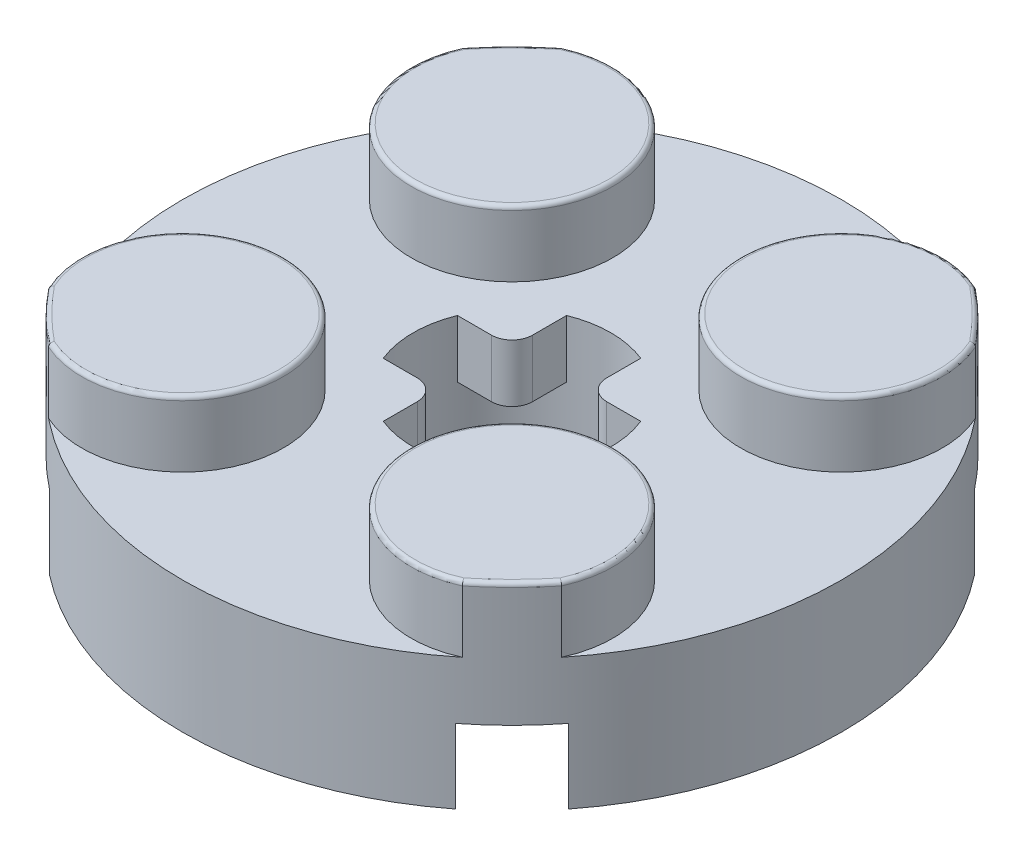
SolidWorks part; units mm, degrees
material "PET"
ref_plane "Alzado" through (0, 0, 0) normal (0, 0, 1) x (1, 0, 0)
ref_plane "Planta" through (0, 0, 0) normal (0, 1, 0) x (1, 0, 0)
ref_plane "Vista lateral" through (0, 0, 0) normal (1, 0, 0) x (0, 0, -1)
sketch "Croquis1" plane through (0, 0, 0) normal (0, 1, 0) x (1, 0, 0)
  line L1 (-4, 4) -> (4, 4)
  line L2 (-4, 4) -> (-4, -4)
  line L3 (-4, -4) -> (4, -4)
  line L4 (4, 4) -> (4, -4)
  line L5 (-4, 4) -> (4, -4) construction
  line L6 (-4, -4) -> (4, 4) construction
  point P0 (0, 0)
  dimension "D1" = 8
extrude "Saliente-Extruir1" add sketch "Croquis1" along normal blind 3.2
sketch "Croquis2" plane through (0, 3.2, 0) normal (0, 1, 0) x (1, 0, 0)
  circle A0 centre (0, 0) radius 2.45
  dimension "D1" = 4.9
extrude "Saliente-Extruir2" add sketch "Croquis2" along normal blind 1.6
mirror "Simetría1" about plane through (4, 3.2, -4) normal (-1, 0, 0) of "Saliente-Extruir2", "Saliente-Extruir1"
mirror "Simetría2" about plane through (-4, 3.2, -4) normal (0, 0, 1) of bodies 105
sketch "Croquis3" plane through (0, 0, 0) normal (0, -1, 0) x (1, 0, 0)
  line L1 (-2.3, -10.3) -> (10.3, -10.3)
  line L2 (-2.3, -10.3) -> (-2.3, 2.3)
  line L3 (-2.3, 2.3) -> (10.3, 2.3)
  line L4 (10.3, -10.3) -> (10.3, 2.3)
  line L5 (-2.3, -10.3) -> (10.3, 2.3) construction
  line L6 (-2.3, 2.3) -> (10.3, -10.3) construction
  line L7 (-4, -12) -> (12, -12) construction
  line L12 (-4, -12) -> (-4, 4) construction
  line L13 (-4, 4) -> (12, 4) construction
  point P0 (4, -4)
  dimension "D1" = 8
  dimension "D2" = 1.7
  dimension "D3" = 8
extrude "Cortar-Extruir1" cut sketch "Croquis3" against normal blind 1.8
sketch "Croquis4" plane through (0, 1.8, 0) normal (0, -1, 0) x (1, 0, 0)
  line L0 (-4, 4) -> (12, 4) construction
  line L1 (-4, -12) -> (-4, 4) construction
  line L2 (4, 2.3) -> (4, -10.3) construction
  line L3 (10.3, 2.3) -> (-2.3, 2.3) construction
  line L4 (-2.3, -10.3) -> (10.3, -10.3) construction
  line L5 (-2.3, -4) -> (10.3, -4) construction
  line L6 (-2.3, 2.3) -> (-2.3, -10.3) construction
  line L7 (10.3, -10.3) -> (10.3, 2.3) construction
  circle A0 centre (0, 0) radius 1.6
  circle A1 centre (8, 0) radius 1.6
  circle A2 centre (0, -8) radius 1.6
  circle A3 centre (8, -8) radius 1.6
  dimension "D1" = 3.2
  dimension "D2" = 4
  dimension "D4" = 2
  dimension "D3" = 4
  dimension "D5" = 2
sketch "Croquis5" plane through (0, 0, 0) normal (0, -1, 0) x (1, 0, 0)
  line L0 (-4, -12) -> (-4, 4) construction
  line L1 (-4, 4) -> (12, 4) construction
  circle A0 centre (4, -4) radius 3.267
  circle A1 centre (4, -4) radius 2.4
  dimension "D1" = 4.8
  dimension "D2" = 8
  dimension "D3" = 8
  dimension "D4" = 6.534
extrude "Saliente-Extruir3" add sketch "Croquis5" against normal up to next
sketch "Croquis6" plane through (0, 3.2, 0) normal (0, 1, 0) x (1, 0, 0)
  line L0 (-4, 12) -> (12, 12) construction
  line L1 (-4, 12) -> (-4, -4) construction
  line L2 (-4, -4) -> (12, -4) construction
  circle A0 centre (4, 4) radius 8
extrude "Cortar-Extruir3" cut sketch "Croquis6" against normal blind 10 flip side to cut
sketch "Croquis7" plane through (0, 3.2, 0) normal (0, 1, 0) x (1, 0, 0)
  line L0 (4, -4) -> (4, 4) construction
  arc A0 (-1.0239, -2.2258) -> (9.0239, -2.2258) centre (4, 4) ccw construction
  line B0 (1.7751, 4.9) -> (1.7751, 3.1) construction
  line B1 (4.9, 6.2249) -> (3.1, 6.2249) construction
  line B2 (6.2249, 4.9) -> (6.2249, 3.1) construction
  line B3 (4.9, 1.7751) -> (3.1, 1.7751) construction
  line B4 (2.6, 4.9) -> (1.7751, 4.9)
  line B5 (4.9, 1.7751) -> (4.9, 2.6)
  line B6 (3.1, 1.7751) -> (3.1, 2.6)
  line B7 (4.9, 1.7751) -> (3.1, 6.2249) construction
  line B8 (4.9, 6.2249) -> (3.1, 1.7751) construction
  line B9 (6.2249, 4.9) -> (5.4, 4.9)
  line B10 (6.2249, 3.1) -> (5.4, 3.1)
  line B11 (6.2249, 4.9) -> (1.7751, 3.1) construction
  line B12 (6.2249, 3.1) -> (1.7751, 4.9) construction
  line B13 (3.1, 5.4) -> (3.1, 6.2249)
  line B14 (4.9, 5.4) -> (4.9, 6.2249)
  line B15 (2.6, 3.1) -> (1.7751, 3.1)
  arc B16 (1.7751, 4.9) -> (1.7751, 3.1) centre (4, 4) ccw
  arc B17 (2.6, 3.1) -> (3.1, 2.6) centre (2.6, 2.6) cw
  arc B18 (4.9, 2.6) -> (5.4, 3.1) centre (5.4, 2.6) cw
  arc B19 (5.4, 4.9) -> (4.9, 5.4) centre (5.4, 5.4) cw
  arc B20 (3.1, 5.4) -> (2.6, 4.9) centre (2.6, 5.4) cw
  arc B21 (4.9, 6.2249) -> (3.1, 6.2249) centre (4, 4) ccw
  arc B22 (6.2249, 3.1) -> (6.2249, 4.9) centre (4, 4) ccw
  arc B23 (3.1, 1.7751) -> (4.9, 1.7751) centre (4, 4) ccw
sketch_block_instance "kereszt-metszet-1"
sketch_block "Bloque1" parameters "D1"=4.8, "D3"=0.5, "D2"=1.8
extrude "Cortar-Extruir4" cut sketch "Croquis7" against normal through all
sketch "Croquis10" plane through (0, 4.8, 0) normal (0, 1, 0) x (1, 0, 0)
  arc A2 (10.1035, -0.6446) -> (8.6446, -2.1035) centre (8, 0) ccw construction
  arc A3 (8.6446, 10.1035) -> (10.1035, 8.6446) centre (8, 8) ccw construction
  line B0 (-1.3419, 8.88) -> (-1.7347, 7.12) construction
  line B1 (-1.2247, 8.8539) -> (-1.585, 7.24)
  line B2 (-1.459, 8.9061) -> (-1.8518, 7.1461)
  line B3 (-1.7347, 7.12) -> (-1.2347, 7.12) construction
  line B4 (-0.4503, 8.88) -> (-0.8432, 7.12) construction
  line B5 (-1.7347, 7) -> (-1.2347, 7)
  line B6 (-0.3542, 8.76) -> (-0.497, 8.12)
  line B7 (-1.585, 7.24) -> (-1.2347, 7.24)
  line B8 (-0.5675, 8.9061) -> (-0.9603, 7.1461)
  line B9 (-0.4503, 8.88) -> (0.0497, 8.88) construction
  line B10 (-0.4503, 9) -> (0.0497, 9)
  line B11 (-0.3542, 8.76) -> (0.0497, 8.76)
  line B12 (-0.6468, 8) -> (-0.3468, 8) construction
  line B13 (-0.5506, 7.88) -> (-0.6935, 7.24)
  line B14 (-0.5506, 7.88) -> (-0.3468, 7.88)
  line B15 (-0.8432, 7.12) -> (-0.3432, 7.12) construction
  line B16 (1.3043, 8.6845) -> (1.0231, 7.4245) construction
  line B17 (-0.8432, 7) -> (-0.3432, 7)
  line B18 (-0.497, 8.12) -> (-0.3468, 8.12)
  line B19 (-0.6935, 7.24) -> (-0.3432, 7.24)
  line B20 (1.4214, 8.6583) -> (1.1402, 7.3983)
  line B21 (1.1872, 8.7106) -> (0.9059, 7.4506)
  line B22 (0.3974, 8.684) -> (0.1163, 7.4245) construction
  line B23 (0.5145, 8.6578) -> (0.2334, 7.3983)
  line B24 (0.2803, 8.7101) -> (-0.0008, 7.4506)
  line B25 (0.6043, 7.3155) -> (0.7571, 8) construction
  line B26 (0.4872, 7.3417) -> (0.6073, 7.88)
  line B27 (0.7214, 7.2894) -> (0.8742, 7.9739)
  line B28 (1.7923, 8.5755) -> (1.5111, 7.3155) construction
  line B29 (1.9094, 8.5494) -> (1.6282, 7.2894)
  line B30 (1.6752, 8.6017) -> (1.3939, 7.3417)
  line B31 (-1.347, 9) -> (1.5483, 9) construction
  line B32 (-1.7347, 7) -> (1.2671, 7) construction
  line B33 (0.7571, 8) -> (0.5771, 8) construction
  line B34 (0.7571, 8.12) -> (0.5771, 8.12)
  line B35 (0.6073, 7.88) -> (0.5771, 7.88)
  line B36 (-1.1147, 7.12) -> (-0.6951, 9) construction
  line B37 (-0.2232, 7.12) -> (0.1583, 8.829) construction
  arc B38 (-1.459, 8.9061) -> (-1.2247, 8.8539) centre (-1.3419, 8.88) cw
  arc B39 (-1.8518, 7.1461) -> (-1.7347, 7) centre (-1.7347, 7.12) ccw
  arc B40 (-1.2347, 7) -> (-1.2347, 7.24) centre (-1.2347, 7.12) ccw
  arc B41 (0.8742, 7.9739) -> (0.7571, 8.12) centre (0.7571, 8) ccw
  arc B42 (0.0497, 8.76) -> (0.0497, 9) centre (0.0497, 8.88) ccw
  arc B43 (0.5771, 8.12) -> (0.5771, 7.88) centre (0.5771, 8) ccw
  arc B44 (-0.3468, 7.88) -> (-0.3468, 8.12) centre (-0.3468, 8) ccw
  arc B45 (-0.9603, 7.1461) -> (-0.8432, 7) centre (-0.8432, 7.12) ccw
  arc B46 (-0.3432, 7) -> (-0.3432, 7.24) centre (-0.3432, 7.12) ccw
  arc B47 (-0.4503, 9) -> (-0.5675, 8.9061) centre (-0.4503, 8.88) ccw
  arc B48 (0.3974, 8.684) -> (0.891, 8.6) centre (0.6421, 8.6293) cw construction
  arc B49 (1.0102, 8.586) -> (0.2803, 8.7101) centre (0.6421, 8.6293) ccw
  arc B50 (0.7718, 8.614) -> (0.5145, 8.6578) centre (0.6421, 8.6293) ccw
  arc B51 (0.7718, 8.614) -> (1.0102, 8.586) centre (0.891, 8.6) ccw
  arc B52 (0.1163, 7.4245) -> (0.6043, 7.3155) centre (0.3603, 7.37) ccw construction
  arc B53 (-0.0008, 7.4506) -> (0.7214, 7.2894) centre (0.3603, 7.37) ccw
  arc B54 (0.2334, 7.3983) -> (0.4872, 7.3417) centre (0.3603, 7.37) ccw
  arc B55 (1.0231, 7.4245) -> (1.5111, 7.3155) centre (1.2671, 7.37) ccw construction
  arc B56 (0.9059, 7.4506) -> (1.6282, 7.2894) centre (1.2671, 7.37) ccw
  arc B57 (1.1402, 7.3983) -> (1.3939, 7.3417) centre (1.2671, 7.37) ccw
  arc B58 (1.3043, 8.6845) -> (1.7923, 8.5755) centre (1.5483, 8.63) cw construction
  arc B59 (1.9094, 8.5494) -> (1.1872, 8.7106) centre (1.5483, 8.63) ccw
  arc B60 (1.6752, 8.6017) -> (1.4214, 8.6583) centre (1.5483, 8.63) ccw
  circle B61 centre (-0.0325, 7.9745) radius 2.4 construction
  line B62 (-1.1923, 0.8794) -> (-1.5525, -0.7345)
  line B63 (-1.4265, 0.9317) -> (-1.8194, -0.8283)
  line B64 (-1.7023, -0.9745) -> (-1.2023, -0.9745)
  line B65 (-0.3217, 0.7855) -> (-0.4646, 0.1455)
  line B66 (-1.5525, -0.7345) -> (-1.2023, -0.7345)
  line B67 (-0.535, 0.9317) -> (-0.9279, -0.8283)
  line B68 (-0.4179, 1.0255) -> (0.0821, 1.0255)
  line B69 (-0.3217, 0.7855) -> (0.0821, 0.7855)
  line B70 (-0.5181, -0.0945) -> (-0.661, -0.7345)
  line B71 (-0.5181, -0.0945) -> (-0.3143, -0.0945)
  line B72 (-0.8107, -0.9745) -> (-0.3107, -0.9745)
  line B73 (-0.4646, 0.1455) -> (-0.3143, 0.1455)
  line B74 (-0.661, -0.7345) -> (-0.3107, -0.7345)
  line B75 (1.4539, 0.6838) -> (1.1726, -0.5762)
  line B76 (1.2197, 0.7361) -> (0.9384, -0.5239)
  line B77 (0.547, 0.6833) -> (0.2659, -0.5762)
  line B78 (0.3128, 0.7356) -> (0.0316, -0.5239)
  line B79 (0.5196, -0.6328) -> (0.6398, -0.0945)
  line B80 (0.7539, -0.6851) -> (0.9066, -0.0006)
  line B81 (1.9419, 0.5749) -> (1.6606, -0.6851)
  line B82 (1.7077, 0.6272) -> (1.4264, -0.6328)
  line B83 (0.7895, 0.1455) -> (0.6095, 0.1455)
  line B84 (0.6398, -0.0945) -> (0.6095, -0.0945)
  arc B85 (-1.4265, 0.9317) -> (-1.1923, 0.8794) centre (-1.3094, 0.9055) cw
  arc B86 (-1.8194, -0.8283) -> (-1.7023, -0.9745) centre (-1.7023, -0.8545) ccw
  arc B87 (-1.2023, -0.9745) -> (-1.2023, -0.7345) centre (-1.2023, -0.8545) ccw
  arc B88 (0.9066, -0.0006) -> (0.7895, 0.1455) centre (0.7895, 0.0255) ccw
  arc B89 (0.0821, 0.7855) -> (0.0821, 1.0255) centre (0.0821, 0.9055) ccw
  arc B90 (0.6095, 0.1455) -> (0.6095, -0.0945) centre (0.6095, 0.0255) ccw
  arc B91 (-0.3143, -0.0945) -> (-0.3143, 0.1455) centre (-0.3143, 0.0255) ccw
  arc B92 (-0.9279, -0.8283) -> (-0.8107, -0.9745) centre (-0.8107, -0.8545) ccw
  arc B93 (-0.3107, -0.9745) -> (-0.3107, -0.7345) centre (-0.3107, -0.8545) ccw
  arc B94 (-0.4179, 1.0255) -> (-0.535, 0.9317) centre (-0.4179, 0.9055) ccw
  arc B95 (1.0426, 0.6115) -> (0.3128, 0.7356) centre (0.6745, 0.6549) ccw
  arc B96 (0.8043, 0.6396) -> (0.547, 0.6833) centre (0.6745, 0.6549) ccw
  arc B97 (0.8043, 0.6396) -> (1.0426, 0.6115) centre (0.9235, 0.6255) ccw
  arc B98 (0.0316, -0.5239) -> (0.7539, -0.6851) centre (0.3927, -0.6045) ccw
  arc B99 (0.2659, -0.5762) -> (0.5196, -0.6328) centre (0.3927, -0.6045) ccw
  arc B100 (0.9384, -0.5239) -> (1.6606, -0.6851) centre (1.2995, -0.6045) ccw
  arc B101 (1.1726, -0.5762) -> (1.4264, -0.6328) centre (1.2995, -0.6045) ccw
  arc B102 (1.9419, 0.5749) -> (1.2197, 0.7361) centre (1.5808, 0.6555) ccw
  arc B103 (1.7077, 0.6272) -> (1.4539, 0.6838) centre (1.5808, 0.6555) ccw
  line B104 (6.8077, 8.8794) -> (6.4475, 7.2655)
  line B105 (6.5735, 8.9317) -> (6.1806, 7.1717)
  line B106 (6.2977, 7.0255) -> (6.7977, 7.0255)
  line B107 (7.6783, 8.7855) -> (7.5354, 8.1455)
  line B108 (6.4475, 7.2655) -> (6.7977, 7.2655)
  line B109 (7.465, 8.9317) -> (7.0721, 7.1717)
  line B110 (7.5821, 9.0255) -> (8.0821, 9.0255)
  line B111 (7.6783, 8.7855) -> (8.0821, 8.7855)
  line B112 (7.4819, 7.9055) -> (7.339, 7.2655)
  line B113 (7.4819, 7.9055) -> (7.6857, 7.9055)
  line B114 (7.1893, 7.0255) -> (7.6893, 7.0255)
  line B115 (7.5354, 8.1455) -> (7.6857, 8.1455)
  line B116 (7.339, 7.2655) -> (7.6893, 7.2655)
  line B117 (9.4539, 8.6838) -> (9.1726, 7.4238)
  line B118 (9.2197, 8.7361) -> (8.9384, 7.4761)
  line B119 (8.547, 8.6833) -> (8.2659, 7.4238)
  line B120 (8.3128, 8.7356) -> (8.0316, 7.4761)
  line B121 (8.5196, 7.3672) -> (8.6398, 7.9055)
  line B122 (8.7539, 7.3149) -> (8.9066, 7.9994)
  line B123 (9.9419, 8.5749) -> (9.6606, 7.3149)
  line B124 (9.7077, 8.6272) -> (9.4264, 7.3672)
  line B125 (8.7895, 8.1455) -> (8.6095, 8.1455)
  line B126 (8.6398, 7.9055) -> (8.6095, 7.9055)
  arc B127 (6.5735, 8.9317) -> (6.8077, 8.8794) centre (6.6906, 8.9055) cw
  arc B128 (6.1806, 7.1717) -> (6.2977, 7.0255) centre (6.2977, 7.1455) ccw
  arc B129 (6.7977, 7.0255) -> (6.7977, 7.2655) centre (6.7977, 7.1455) ccw
  arc B130 (8.9066, 7.9994) -> (8.7895, 8.1455) centre (8.7895, 8.0255) ccw
  arc B131 (8.0821, 8.7855) -> (8.0821, 9.0255) centre (8.0821, 8.9055) ccw
  arc B132 (8.6095, 8.1455) -> (8.6095, 7.9055) centre (8.6095, 8.0255) ccw
  arc B133 (7.6857, 7.9055) -> (7.6857, 8.1455) centre (7.6857, 8.0255) ccw
  arc B134 (7.0721, 7.1717) -> (7.1893, 7.0255) centre (7.1893, 7.1455) ccw
  arc B135 (7.6893, 7.0255) -> (7.6893, 7.2655) centre (7.6893, 7.1455) ccw
  arc B136 (7.5821, 9.0255) -> (7.465, 8.9317) centre (7.5821, 8.9055) ccw
  arc B137 (9.0426, 8.6115) -> (8.3128, 8.7356) centre (8.6745, 8.6549) ccw
  arc B138 (8.8043, 8.6396) -> (8.547, 8.6833) centre (8.6745, 8.6549) ccw
  arc B139 (8.8043, 8.6396) -> (9.0426, 8.6115) centre (8.9235, 8.6255) ccw
  arc B140 (8.0316, 7.4761) -> (8.7539, 7.3149) centre (8.3927, 7.3955) ccw
  arc B141 (8.2659, 7.4238) -> (8.5196, 7.3672) centre (8.3927, 7.3955) ccw
  arc B142 (8.9384, 7.4761) -> (9.6606, 7.3149) centre (9.2995, 7.3955) ccw
  arc B143 (9.1726, 7.4238) -> (9.4264, 7.3672) centre (9.2995, 7.3955) ccw
  arc B144 (9.9419, 8.5749) -> (9.2197, 8.7361) centre (9.5808, 8.6555) ccw
  arc B145 (9.7077, 8.6272) -> (9.4539, 8.6838) centre (9.5808, 8.6555) ccw
  line B146 (6.8077, 0.8794) -> (6.4475, -0.7345)
  line B147 (6.5735, 0.9317) -> (6.1806, -0.8283)
  line B148 (6.2977, -0.9745) -> (6.7977, -0.9745)
  line B149 (7.6783, 0.7855) -> (7.5354, 0.1455)
  line B150 (6.4475, -0.7345) -> (6.7977, -0.7345)
  line B151 (7.465, 0.9317) -> (7.0721, -0.8283)
  line B152 (7.5821, 1.0255) -> (8.0821, 1.0255)
  line B153 (7.6783, 0.7855) -> (8.0821, 0.7855)
  line B154 (7.4819, -0.0945) -> (7.339, -0.7345)
  line B155 (7.4819, -0.0945) -> (7.6857, -0.0945)
  line B156 (7.1893, -0.9745) -> (7.6893, -0.9745)
  line B157 (7.5354, 0.1455) -> (7.6857, 0.1455)
  line B158 (7.339, -0.7345) -> (7.6893, -0.7345)
  line B159 (9.4539, 0.6838) -> (9.1726, -0.5762)
  line B160 (9.2197, 0.7361) -> (8.9384, -0.5239)
  line B161 (8.547, 0.6833) -> (8.2659, -0.5762)
  line B162 (8.3128, 0.7356) -> (8.0316, -0.5239)
  line B163 (8.5196, -0.6328) -> (8.6398, -0.0945)
  line B164 (8.7539, -0.6851) -> (8.9066, -0.0006)
  line B165 (9.9419, 0.5749) -> (9.6606, -0.6851)
  line B166 (9.7077, 0.6272) -> (9.4264, -0.6328)
  line B167 (8.7895, 0.1455) -> (8.6095, 0.1455)
  line B168 (8.6398, -0.0945) -> (8.6095, -0.0945)
  arc B169 (6.5735, 0.9317) -> (6.8077, 0.8794) centre (6.6906, 0.9055) cw
  arc B170 (6.1806, -0.8283) -> (6.2977, -0.9745) centre (6.2977, -0.8545) ccw
  arc B171 (6.7977, -0.9745) -> (6.7977, -0.7345) centre (6.7977, -0.8545) ccw
  arc B172 (8.9066, -0.0006) -> (8.7895, 0.1455) centre (8.7895, 0.0255) ccw
  arc B173 (8.0821, 0.7855) -> (8.0821, 1.0255) centre (8.0821, 0.9055) ccw
  arc B174 (8.6095, 0.1455) -> (8.6095, -0.0945) centre (8.6095, 0.0255) ccw
  arc B175 (7.6857, -0.0945) -> (7.6857, 0.1455) centre (7.6857, 0.0255) ccw
  arc B176 (7.0721, -0.8283) -> (7.1893, -0.9745) centre (7.1893, -0.8545) ccw
  arc B177 (7.6893, -0.9745) -> (7.6893, -0.7345) centre (7.6893, -0.8545) ccw
  arc B178 (7.5821, 1.0255) -> (7.465, 0.9317) centre (7.5821, 0.9055) ccw
  arc B179 (9.0426, 0.6115) -> (8.3128, 0.7356) centre (8.6745, 0.6549) ccw
  arc B180 (8.8043, 0.6396) -> (8.547, 0.6833) centre (8.6745, 0.6549) ccw
  arc B181 (8.8043, 0.6396) -> (9.0426, 0.6115) centre (8.9235, 0.6255) ccw
  arc B182 (8.0316, -0.5239) -> (8.7539, -0.6851) centre (8.3927, -0.6045) ccw
  arc B183 (8.2659, -0.5762) -> (8.5196, -0.6328) centre (8.3927, -0.6045) ccw
  arc B184 (8.9384, -0.5239) -> (9.6606, -0.6851) centre (9.2995, -0.6045) ccw
  arc B185 (9.1726, -0.5762) -> (9.4264, -0.6328) centre (9.2995, -0.6045) ccw
  arc B186 (9.9419, 0.5749) -> (9.2197, 0.7361) centre (9.5808, 0.6555) ccw
  arc B187 (9.7077, 0.6272) -> (9.4539, 0.6838) centre (9.5808, 0.6555) ccw
sketch_block_instance "Bloque4-1"
sketch_block "Bloque4" parameters "D17"=4.8, "D1"=2, "D2"=0.24, "D3"=0.5, "D4"=77.417, "D5"=0.24, "D6"=0.24, "D7"=0.3, "D8"=0.24, "D9"=0.5, "D10"=0.18, "D11"=1.6, "D12"=0.24, "D13"=0.5, "D14"=0.145, "D15"=0.145, "D16"=0.145
sketch_block_instance "Bloque4-2"
sketch_block_instance "Bloque4-4"
sketch_block_instance "Bloque4-5"
extrude "Cut-Extrude-Thin1" cut sketch "Croquis6<3>" along normal through all flip side to cut thin thin type one direction wall 1
sketch "Croquis6<3>" plane through (0, 3.2, 0) normal (0, 1, 0) x (1, 0, 0) same geometry as "Croquis6"
extrude "LEGO Logo" [suppressed] add sketch "Croquis10" along normal blind 0.08
fillet "Redondeo4" radius 0.1 8 edges at (6.2676, 4.8, -1.7324) (1.7324, 4.8, -1.7324) (6.2676, 4.8, -6.2676) (1.7324, 4.8, -6.2676) (9.6569, 4.8, 1.6569) (-1.6569, 4.8, 1.6569) (9.6569, 4.8, -9.6569) (-1.6569, 4.8, -9.6569)
